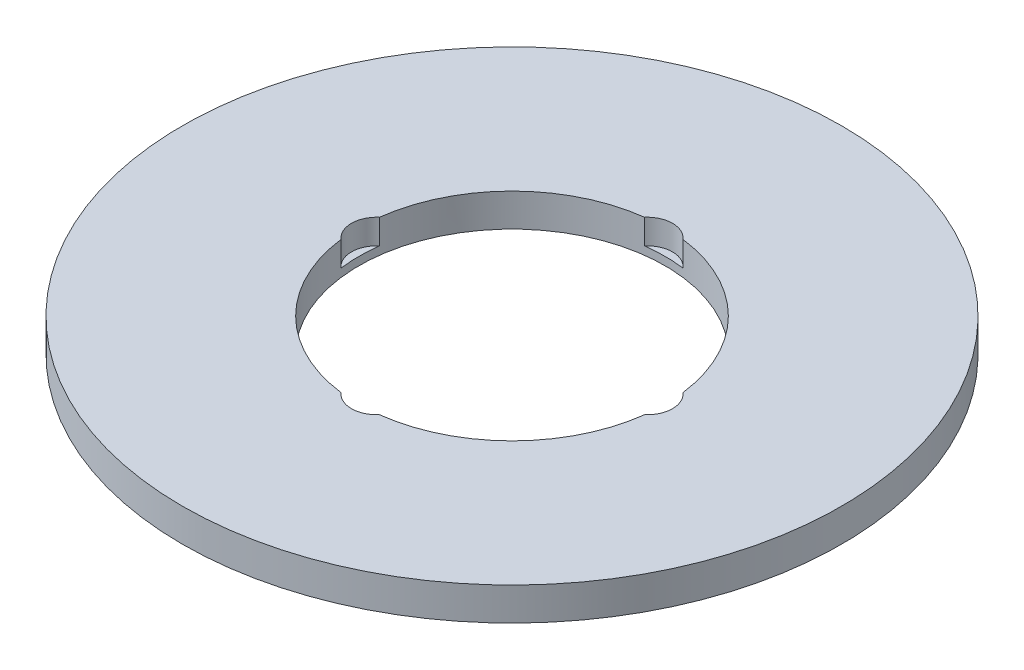
SolidWorks part; units mm, degrees
ref_plane "Front Plane" through (0, 0, 0) normal (0, 0, 1) x (1, 0, 0)
ref_plane "Top Plane" through (0, 0, 0) normal (0, 1, 0) x (1, 0, 0)
ref_plane "Right Plane" through (0, 0, 0) normal (1, 0, 0) x (0, 0, -1)
sketch "Sketch1" plane through (0, 0, 0) normal (0, 1, 0) x (1, 0, 0)
  circle A0 centre (0, 0) radius 70
  dimension "FLANGE_OD" = 140
extrude "Boss-Extrude1" add sketch "Sketch1" along normal blind 7
sketch "Sketch2" plane through (0, 0, 0) normal (0, 1, 0) x (1, 0, 0)
  circle A0 centre (0, 0) radius 32.5
  dimension "BORE_D" = 65
extrude "Cut-Extrude1" cut sketch "Sketch2" along normal through all
sketch "Sketch3" plane through (0, 7, 0) normal (0, 1, 0) x (1, 0, 0)
  circle A0 centre (0, 0) radius 28.7064 construction
  circle A1 centre (-28.7064, 0) radius 5.3965
  dimension "BOLT_D" = 10.7929
  dimension "BOLT_PCD" = 57.4127
extrude "Cut-Extrude2" cut sketch "Sketch3" against normal blind 5.2687
pattern_circular "CirPattern1" count 4 over 360 about axis through (0, 0, 0) along (0, 1, 0) of "Cut-Extrude2"
